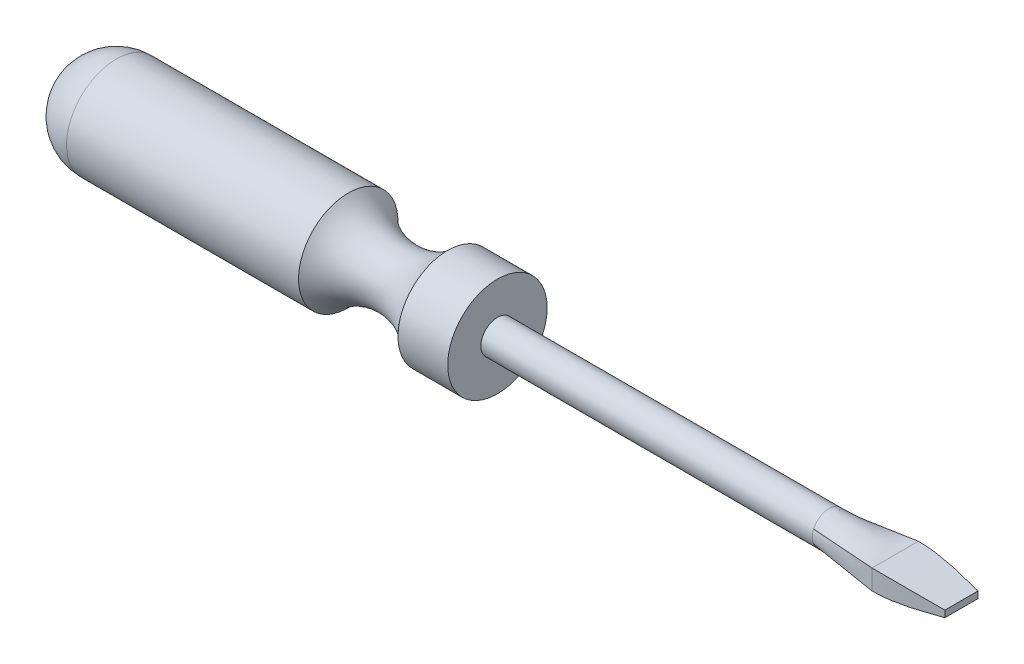
SolidWorks part; units mm, degrees
ref_plane "Front Plane" through (0, 0, 0) normal (1, 0, 0) x (0, 1, 0)
ref_plane "Top Plane" through (0, 0, 0) normal (0, 0, 1) x (0, 1, 0)
ref_plane "Right Plane" through (0, 0, 0) normal (0, 1, 0) x (-1, 0, 0)
sketch "Sketch3" plane through (0, 0, 0) normal (0, 0, 1) x (0, 1, 0)
  line L0 (0, 0) -> (0, 165.1)
  line L1 (19.05, 146.05) -> (19.05, 57.15)
  line L2 (19.05, 19.05) -> (19.05, 0)
  line L3 (19.05, 0) -> (0, 0)
  line L4 (0, 165.1) -> (-19.2923, 165.1) construction
  line L5 (0, 0) -> (0, -127)
  line L6 (0, -127) -> (6.35, -127)
  line L7 (6.35, -127) -> (6.35, 0)
  arc A0 (0, 165.1) -> (19.05, 146.05) centre (0, 146.05) cw
  arc A1 (19.05, 57.15) -> (19.05, 19.05) centre (35.8505, 38.1) ccw
  dimension "D1" = 19.05
  dimension "D4" = 25.4
  dimension "D2" = 38.1
  dimension "D3" = 19.05
  dimension "D5" = 165.1
  dimension "D6" = 6.35
  dimension "D7" = 127
revolve "Revolve2" add sketch "Sketch3" angle 360 about L0 region at (-83.9571, 8.8984, 0)
sketch "Sketch6" plane through (0, 0, 0) normal (1, 0, 0) x (0, 1, 0)
  circle A0 centre (0, 0) radius 19.05 construction
  circle A1 centre (0, 0) radius 19.05
  circle A2 centre (0, 0) radius 6.35
  dimension "D1" = 12.7
ref_plane "Plane3" through (127, 0, 0) normal (1, 0, 0) x (0, 0, -1)
sketch "Sketch7" plane through (127, 0, 0) normal (1, 0, 0) x (0, 0, -1)
  circle A0 centre (0, 0) radius 6.35 construction
  circle A1 centre (0, 0) radius 6.35
  point P3 (0, 0)
ref_plane "Plane1" through (152.4, 0, 0) normal (1, 0, 0) x (0, 0, -1)
ref_plane "Plane2" through (177.8, 0, 0) normal (1, 0, 0) x (0, 0, -1)
sketch "Sketch4" plane through (152.4, 0, 0) normal (1, 0, 0) x (0, 0, -1)
  line L1 (-8.89, 3.81) -> (8.89, 3.81)
  line L2 (-8.89, 3.81) -> (-8.89, -3.81)
  line L3 (-8.89, -3.81) -> (8.89, -3.81)
  line L4 (8.89, 3.81) -> (8.89, -3.81)
  line L5 (-8.89, 3.81) -> (8.89, -3.81) construction
  line L6 (-8.89, -3.81) -> (8.89, 3.81) construction
  circle A2 centre (0, 0) radius 19.05 construction
  circle A3 centre (0, 0) radius 19.05 construction
  point P1 (-0.2403, 7.238)
  point P3 (0, 0)
  point P8 (0, 0)
  point P9 (0, 0)
  point P11 (0, 0)
  point P12 (0, 0)
  point P13 (0, 0)
  dimension "D1" = 7.62
  dimension "D2" = 17.78
sketch "Sketch5" plane through (177.8, 0, 0) normal (1, 0, 0) x (0, 0, -1)
  line L1 (-6.35, -1.27) -> (6.35, -1.27)
  line L2 (-6.35, -1.27) -> (-6.35, 1.27)
  line L3 (-6.35, 1.27) -> (6.35, 1.27)
  line L4 (6.35, -1.27) -> (6.35, 1.27)
  line L5 (-6.35, -1.27) -> (6.35, 1.27) construction
  line L6 (-6.35, 1.27) -> (6.35, -1.27) construction
  point P0 (0, 0)
  point P2 (0, 0)
  dimension "D1" = 12.7
  dimension "D2" = 2.54
extrude "Boss-Extrude1" add sketch "Sketch6" along normal up to vertex (127 mm away) contours A2 region at (0, 0, 0) up to point (127, 0, 0)
loft "Loft5" add profiles "Sketch7", "Sketch4" connector at (127, 0, -6.35) connector at (152.4, 3.81, -8.89)
loft "Loft6" add profiles "Sketch5", "Sketch4<4>" end constraint normal to profile end tangent length 1 connector at (177.8, 1.27, 6.35) connector at (152.4, 3.81, 8.89)
sketch "Sketch4<4>" plane through (152.4, 0, 0) normal (1, 0, 0) x (0, 0, -1) same geometry as "Sketch4"
